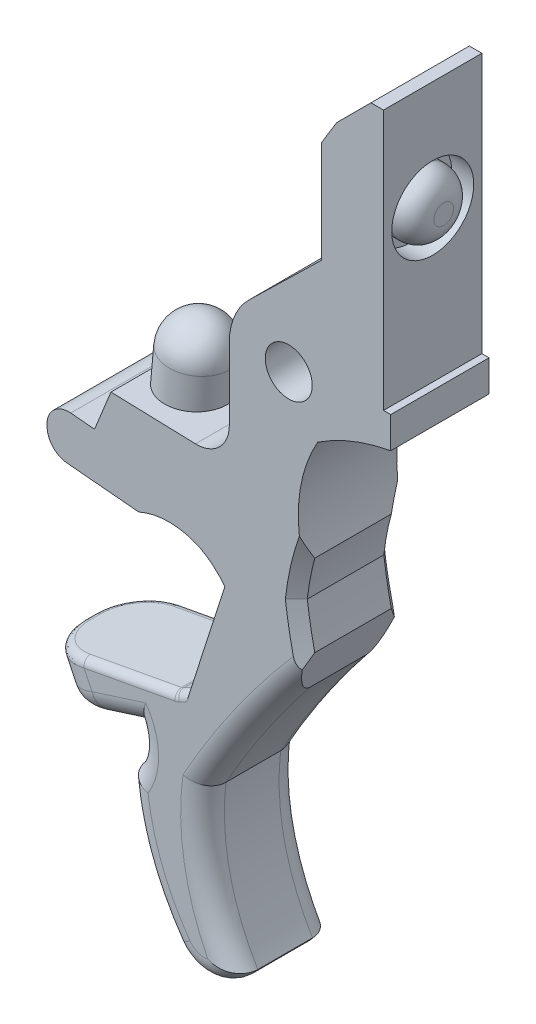
SolidWorks part; units mm, degrees
ref_plane "정면" through (0, 0, 0) normal (0, 0, 1) x (1, 0, 0)
ref_plane "윗면" through (0, 0, 0) normal (0, 1, 0) x (1, 0, 0)
ref_plane "우측면" through (0, 0, 0) normal (1, 0, 0) x (0, 0, -1)
sketch "스케치1" plane through (0, 0, 0) normal (0, 0, 1) x (1, 0, 0)
  line L0 (7.5189, 25.0781) -> (8.6691, 25.0781)
  line L1 (7.5189, 25.0781) -> (4.3842, 21.9434)
  line L2 (8.6691, 25.0781) -> (8.6691, 1.2815)
  line L3 (-5.4378, 0) -> (-5.4378, -10.0581)
  line L4 (-17.7666, -13.4266) -> (-19.9405, -13.2288)
  line L5 (2.9878, 19.65) -> (2.9878, 17.6612)
  line L6 (-20.2877, -17.3633) -> (-13.717, -17.9611)
  line L7 (2.9878, 17.6612) -> (2.9878, 10.3289)
  line L9 (-5.8474, -19.9317) -> (-9.1945, -30.3519)
  line L10 (2.2148, 21.9434) -> (4.3842, 21.9434) construction
  line L11 (4.3842, 21.9434) -> (2.9878, 19.65)
  line L12 (-9.1945, -30.3519) -> (-23.0984, -32.9276)
  line L13 (-5.4378, -10.0581) -> (-16.2648, -9.7282)
  line L14 (-16.2648, -9.7282) -> (-17.7666, -13.4266)
  line L15 (-23.0984, -32.9276) -> (-20.977, -37.3806)
  line L16 (8.6691, 21.9434) -> (17.8049, 21.9434) construction
  line L17 (-14.0961, -35.1913) -> (-20.977, -37.3806)
  line L18 (9.3257, -1.5863) -> (9.3257, 1.2815)
  line L19 (0, -25.9504) -> (1.3829, -22.0511)
  line L20 (9.3257, 1.2815) -> (8.6691, 1.2815)
  line L22 (2.9878, 10.3289) -> (-3.622, 3.8974)
  line L23 (-5.4378, -0.4029) -> (-5.4378, 0)
  circle A0 centre (0, 0) radius 2.15
  arc A1 (-3.622, 3.8974) -> (-5.4378, -0.4029) centre (0.5622, -0.4029) ccw
  arc A2 (0.6986, -18.1472) -> (1.3829, -22.0511) centre (41.5962, -12.9908) ccw
  arc A3 (-7.7429, -37.3806) -> (-4.8219, -50.7518) centre (13.1114, -39.8297) ccw
  arc A4 (-13.717, -17.9611) -> (-8.0435, -18.0339) centre (-10.9576, -24.0227) cw
  arc A5 (-22.1027, -15.4958) -> (-20.2877, -17.3633) centre (-20.1065, -15.3716) ccw
  arc A6 (-19.9405, -13.2288) -> (-22.1027, -15.4958) centre (-20.1217, -15.2206) ccw
  arc A7 (2.6519, -4.2388) -> (1.3829, -14.5653) centre (14.2652, -10.9071) ccw
  arc A8 (-4.8219, -50.7518) -> (-10.6638, -50.7518) centre (-7.7429, -48.6659) cw
  arc A9 (-7.7429, -37.3806) -> (0, -25.9504) centre (65.9603, -78.9697) cw
  arc A10 (-8.0435, -18.0339) -> (-5.8474, -19.9317) centre (-11.4602, -24.2072) cw
  arc A12 (2.6519, -4.2388) -> (9.3257, -1.5863) centre (12.4538, -19.1791) cw
  arc A13 (1.3829, -14.5653) -> (0.6986, -18.1472) centre (24.1804, -20.7766) ccw
  arc A17 (-10.6638, -50.7518) -> (-14.9428, -39.2662) centre (8.4832, -37.0786) cw
  arc A18 (-14.9428, -39.2662) -> (-14.0961, -35.1913) centre (-18.2374, -36.4562) ccw
  dimension "D1" = 4.3
  dimension "D2" = 6
  dimension "D4" = 2
  dimension "D3" = 45
extrude "보스-돌출1" add sketch "스케치1" along normal blind 9 contours L1 L10 L2 L0 | L10 L11 L5 L7 A1 A12 L18 L20 L2 A0 | A13 A7 L3 L13 L14 L4 A6 A5 L6 A4 A10 L9 L12 L15 A9 L19 A2 region at (-4.6244, -14.8045, 0)
sketch "스케치2" plane through (8.6691, 0, 0) normal (1, 0, 0) x (0, 0, -1)
  line L0 (-9, 25.0781) -> (0, 25.0781) construction
  circle A0 centre (-4.5, 15.0781) radius 3.75
  dimension "D1" = 7.5
  dimension "D2" = 10
extrude "컷-돌출1" cut sketch "스케치2" against normal blind 2
sketch "스케치3" plane through (6.6691, 0, 0) normal (1, 0, 0) x (0, 0, -1)
  circle A0 centre (-4.5, 15.0781) radius 2.9
  dimension "D1" = 5.8
extrude "보스-돌출2" add sketch "스케치3" along normal blind 3
fillet "필렛1" radius 2 1 edges at (9.6691, 17.9781, 4.5)
sketch "스케치4" plane through (-1.3573, -14.9194, 0) normal (0.0906, 0.9959, 0) x (0.9959, -0.0906, 0)
  line L0 (-4.0974, -9) -> (-4.0974, 0) construction
  circle A0 centre (-12.0974, -4.5) radius 2.9
  point P2 (-4.0974, -4.5)
  dimension "D1" = 5.8
  dimension "D2" = 8
extrude "보스-돌출3" add sketch "스케치4" along normal blind 10
fillet "필렛2" radius 2.9 1 edges at (-15.387, -3.6018, 4.5)
fillet "필렛3" radius 3 1 edges at (-5.4378, -10.0581, 4.5)
fillet "필렛4" radius 4 2 edges at (-22.0377, -35.1541, 0) (-22.0377, -35.1541, 9)
chamfer "모따기1" distance 0.5 angle 45 1 edges at (-9.1945, -30.3519, 4.5) first distance on face at (-7.521, -25.1418, 4.5)
fillet "필렛7" radius 0.7 8 edges at (-14.7157, -31.3747, 9) (-21.9059, -32.7067, 7.8284) (-23.0984, -32.9276, 4.5) (-21.9059, -32.7067, 1.1716) (-14.7157, -31.3747, 0) (-10.4045, -30.576, 4.5) (-9.723, -30.2259, 0) (-9.723, -30.2259, 9)
chamfer "모따기2" distance 1 angle 45 4 edges at (0.9938, -20.1074, 0) (0.9716, -16.343, 0) (0.9716, -16.343, 9) (0.9938, -20.1074, 9)
fillet "필렛8" radius 2 15 edges at (-4.1049, -31.5074, 0) (-4.1049, -31.5074, 9) (-7.7429, -52.2552, 9) (-7.7429, -52.2552, 0) (-13.9978, -37.3372, 0) (-13.9978, -37.3372, 9) (-13.5643, -45.2925, 9) (-13.5643, -45.2925, 0) (-7.4024, -44.3109, 0) (-7.4024, -44.3109, 9) (-15.6128, -35.6739, 9) (-15.6128, -35.6739, 0) (-19.8501, -37.0221, 1.1716) (-20.977, -37.3806, 4.5) (-19.8501, -37.0221, 7.8284)
